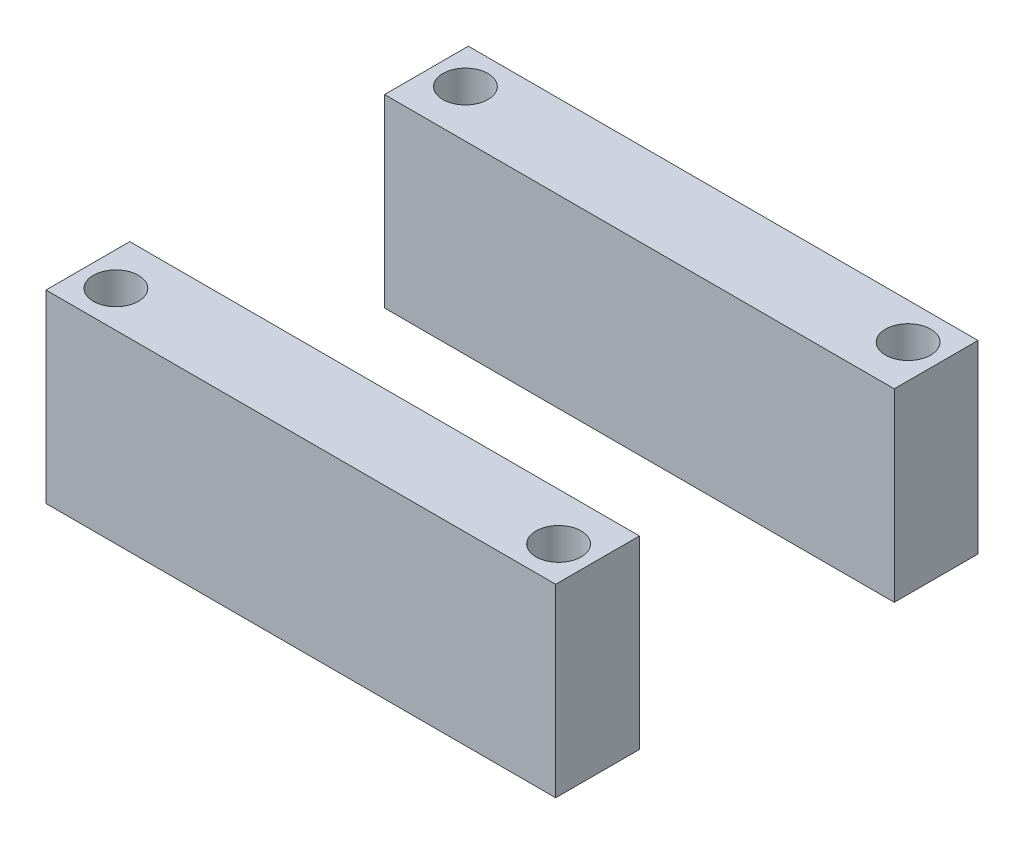
SolidWorks part; units mm, degrees
material "ABS"
ref_plane "Front Plane" through (0, 0, 0) normal (0, 0, 1) x (1, 0, 0)
ref_plane "Top Plane" through (0, 0, 0) normal (0, 1, 0) x (1, 0, 0)
ref_plane "Right Plane" through (0, 0, 0) normal (1, 0, 0) x (0, 0, -1)
sketch "Sketch1" plane through (0, 0, 0) normal (0, 1, 0) x (1, 0, 0)
  line L0 (0, 0) -> (0, 5.7699) construction
  line L1 (-17.5, 14.5) -> (17.5, 14.5)
  line L2 (-17.5, 14.5) -> (-17.5, -14.5)
  line L3 (-17.5, -14.5) -> (17.5, -14.5)
  line L4 (17.5, 14.5) -> (17.5, -14.5)
  line L5 (-17.5, 14.5) -> (17.5, -14.5) construction
  line L6 (-17.5, -14.5) -> (17.5, 14.5) construction
  line L7 (0, 0) -> (-7.7865, 0) construction
  circle A0 centre (-15.2, 12) radius 1.55
  circle A1 centre (15.2, 12) radius 1.55
  circle A2 centre (-15.2, -12) radius 1.55
  circle A3 centre (15.2, -12) radius 1.55
  point P0 (0, 0)
  dimension "D3" = 3.1
  dimension "D4" = 2.5
  dimension "D5" = 2.3
  dimension "D1" = 35
  dimension "D2" = 29
extrude "Boss-Extrude1" add sketch "Sketch1" along normal blind 12.7
sketch "Sketch2" plane through (0, 12.7, 0) normal (0, 1, 0) x (1, 0, 0)
  line L0 (-17.5, 14.5) -> (-17.5, -14.5) construction
  line L1 (-17.5, 8.75) -> (17.5, 8.75)
  line L2 (-17.5, 8.75) -> (-17.5, -8.75)
  line L3 (-17.5, -8.75) -> (17.5, -8.75)
  line L4 (17.5, 8.75) -> (17.5, -8.75)
  line L5 (17.5, -14.5) -> (17.5, 14.5) construction
  line L6 (17.5, 14.5) -> (-17.5, 14.5) construction
  line L7 (-17.5, -14.5) -> (17.5, -14.5) construction
  dimension "D1" = 5.75
  dimension "D2" = 5.75
extrude "Cut-Extrude1" cut sketch "Sketch2" against normal through all
